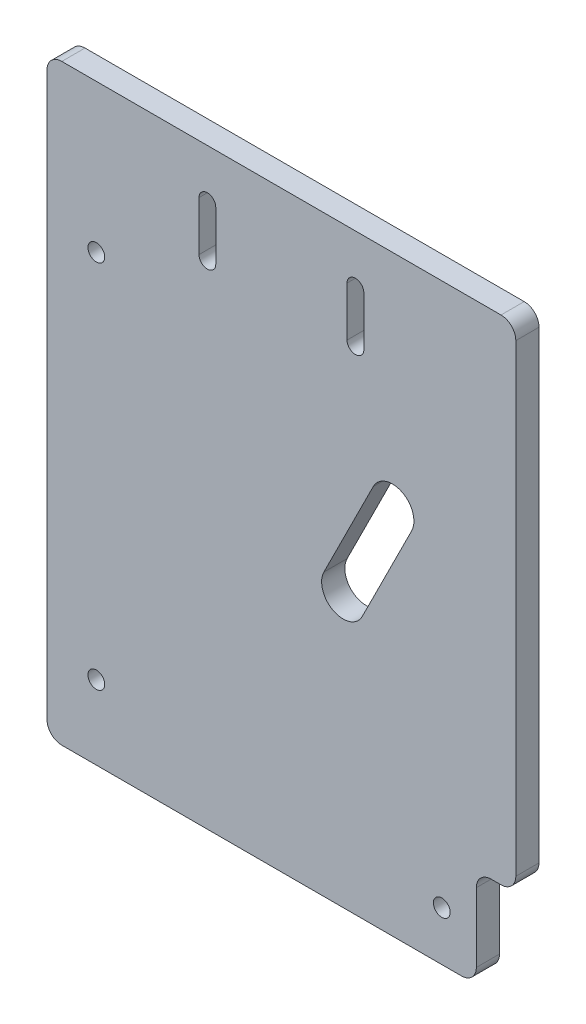
SolidWorks part; units mm, degrees
material "Acrylic (Medium-high impact)"
ref_plane "Front Plane" through (0, 0, 0) normal (0, 0, 1) x (1, 0, 0)
ref_plane "Top Plane" through (0, 0, 0) normal (0, 1, 0) x (1, 0, 0)
ref_plane "Right Plane" through (0, 0, 0) normal (1, 0, 0) x (0, 0, -1)
sketch "Sketch1" plane through (0, 0, 0) normal (0, 0, 1) x (1, 0, 0)
  line L0 (47.5, 0) -> (47.5, -120) construction
  line L1 (0, 0) -> (95, 0)
  line L2 (0, 0) -> (0, -120)
  line L3 (0, -120) -> (95, -120)
  line L4 (95, 0) -> (95, -120)
  line L5 (66.1092, -43.0546) -> (56.1092, -63.0546)
  line L6 (63.8908, -66.9454) -> (73.8908, -46.9454)
  circle A0 centre (60, -65) radius 4.35
  circle A1 centre (10, -30) radius 1.7
  circle A2 centre (10, -105) radius 1.7
  circle A3 centre (80, -110) radius 1.7
  circle A6 centre (70, -45) radius 4.35
  dimension "D4" = 8.7
  dimension "D8" = 3.4
  dimension "D9" = 3.4
  dimension "D11" = 8.7
  dimension "D14" = 3.4
  dimension "D1" = 120
  dimension "D2" = 95
  dimension "D3" = 60
  dimension "D5" = 55
  dimension "D6" = 15
  dimension "D7" = 75
  dimension "D10" = 10
  dimension "D12" = 10
  dimension "D13" = 20
  dimension "D15" = 10
  dimension "D16" = 15
extrude "Boss-Extrude1" add sketch "Sketch1" along normal blind 4.7 contours L0 L1 L2 L3 A2 A1 | L1 L0 L3 L4 A6 L6 A0 L5 region at (71.5274, -60.1501, 0) region at (23.7939, -59.976, 0)
fillet "Fillet1" radius 3 4 edges at (95, -120, 2.35) (0, -120, 2.35) (95, 0, 2.35) (0, 0, 2.35)
sketch "Sketch2" plane through (0, 0, 4.7) normal (0, 0, 1) x (1, 0, 0)
  line L0 (3, 0) -> (92, 0) construction
  line L1 (32.5, -10) -> (62.5, -10) construction
  line L2 (47.5, 0) -> (47.5, -120) construction
  line L3 (3, -120) -> (92, -120) construction
  line L4 (30.8, -10) -> (30.8, -20)
  line L5 (34.2, -10) -> (34.2, -20)
  line L6 (60.8, -10) -> (60.8, -20)
  line L7 (64.2, -10) -> (64.2, -20)
  arc A0 (34.2, -10) -> (30.8, -10) centre (32.5, -10) ccw
  arc A1 (64.2, -10) -> (60.8, -10) centre (62.5, -10) ccw
  arc A2 (30.8, -20) -> (34.2, -20) centre (32.5, -20) ccw
  arc A3 (60.8, -20) -> (64.2, -20) centre (62.5, -20) ccw
  point P10 (47.5, -10)
  dimension "D3" = 3.4
  dimension "D4" = 3.4
  dimension "D1" = 30
  dimension "D2" = 110
  dimension "D5" = 10
extrude "Cut-Extrude1" cut sketch "Sketch2" against normal blind 10
sketch "Sketch3" plane through (0, 0, 4.7) normal (0, 0, 1) x (1, 0, 0)
  line L0 (95, -3) -> (95, -117) construction
  line L1 (95, -100) -> (87, -100)
  line L2 (95, -100) -> (95, -120)
  line L3 (95, -120) -> (87, -120)
  line L4 (87, -100) -> (87, -120)
  line L5 (3, -120) -> (92, -120) construction
  dimension "D1" = 8
  dimension "D2" = 20
extrude "Cut-Extrude2" cut sketch "Sketch3" against normal through all
fillet "Fillet2" radius 3 3 edges at (87, -120, 2.35) (87, -100, 2.35) (95, -100, 2.35)
equation "\"D11@Sketch1\"=\"D4@Sketch1\""
